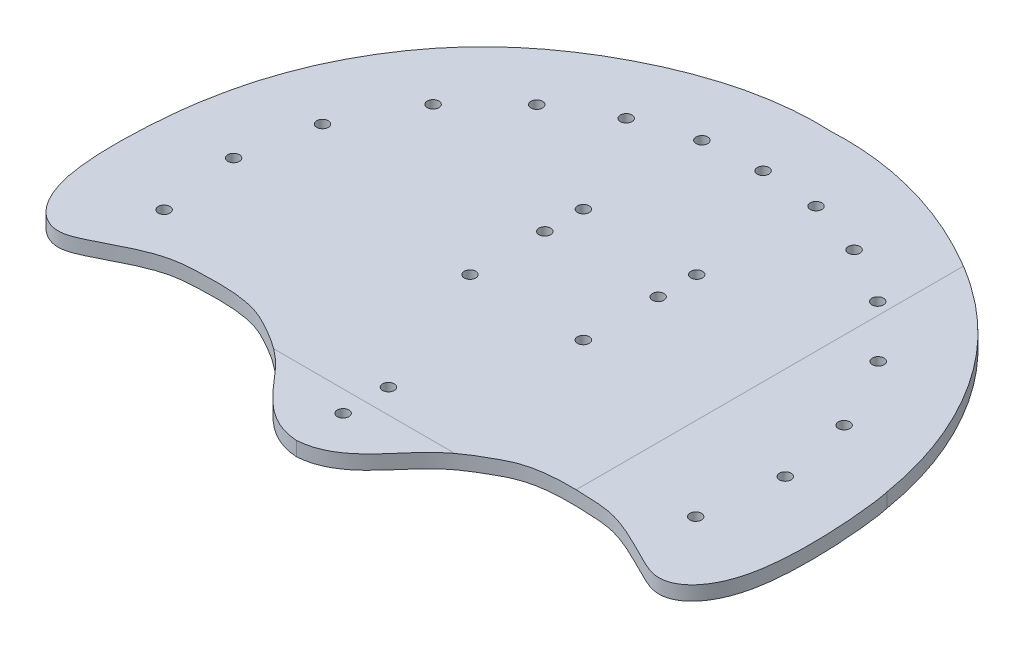
SolidWorks part; units mm, degrees
material "6061-T6 (SS)"
ref_plane "Front Plane" through (0, 0, 0) normal (0, 0, 1) x (1, 0, 0)
ref_plane "Top Plane" through (0, 0, 0) normal (0, 1, 0) x (1, 0, 0)
ref_plane "Right Plane" through (0, 0, 0) normal (1, 0, 0) x (0, 0, -1)
sketch "Sketch3" plane through (0, 0, 0) normal (0, 1, 0) x (1, 0, 0)
  line L0 (0, 0) -> (0, 159.1899) construction
  line L1 (0, 0) -> (0, -140.5301) construction
  line L2 (0, 0) -> (-190.5, 0) construction
  line L3 (0, 0) -> (190.5, 0) construction
  spline S0 degree 3 poles (-190.5, 0) (-184.3927, 37.537) (-157.2613, 93.9641) (-82.3875, 146.6227) (-31.3114, 160.7999) (0, 159.1899) knots 0 0 0 0 0.424401 0.65637 1 1 1 1
  spline S1 degree 3 poles (-190.5, 0) (-192.064, -4.9635) (-201.9672, -83.3146) (-174.6966, -109.29) (-151.6301, -100.568) (-131.4108, -87.7198) (-96.8436, -85.3754) (-78.6925, -86.2588) (-58.8335, -96.8794) (-37.3059, -109.9358) (-21.3496, -139.1148) (0, -140.5301) knots 0 0 0 0 0.166997 0.292321 0.319633 0.426735 0.458914 0.609242 0.64191 0.766802 1 1 1 1
  spline S2 degree 3 poles (190.5, 0) (192.064, -4.9635) (201.9672, -83.3146) (174.6966, -109.29) (151.6301, -100.568) (131.4108, -87.7198) (96.8436, -85.3754) (78.6925, -86.2588) (58.8335, -96.8794) (37.3059, -109.9358) (21.3496, -139.1148) (0, -140.5301) knots 0 0 0 0 0.166997 0.292321 0.319633 0.426735 0.458914 0.609242 0.64191 0.766802 1 1 1 1
  spline S3 degree 3 poles (190.5, 0) (184.3927, 37.537) (157.2613, 93.9641) (82.3875, 146.6227) (31.3114, 160.7999) (0, 159.1899) knots 0 0 0 0 0.424401 0.65637 1 1 1 1
  dimension "D1" = 381
  dimension "D2" = 299.72
  dimension "D3" = 159.1899
  dimension "D4" = 86.8953
  dimension "D5" = 104.4979
  dimension "D6" = 29.1616
  dimension "D7" = 92.2742
  dimension "D8" = 108.411
  dimension "D9" = 67.4883
  dimension "D10" = 43.7314
  dimension "D11" = 117.6915
  dimension "D12" = 162.2568
  dimension "D13" = 89.4522
  dimension "D14" = 140.1036
  dimension "D15" = 175.0666
  dimension "D16" = 50.2669
  dimension "D17" = 101.3666
  dimension "D18" = 138.1225
  dimension "D19" = 155.1557
  dimension "D20" = 192.0074
  dimension "D21" = 193.9268
  dimension "D23" = 76.6666
extrude "Boss-Extrude1" add sketch "Sketch3" along normal blind 7.9502 from surface starting at plane "Top Plane"
sketch "Sketch5" plane through (0, 0, 0) normal (0, -1, 0) x (1, 0, 0)
  line L0 (0, 0) -> (0, -20.32) construction
  line L1 (31.75, -52.07) -> (-31.75, -52.07)
  line L2 (31.75, -52.07) -> (31.75, 11.43)
  line L3 (31.75, 11.43) -> (-31.75, 11.43)
  line L4 (-31.75, -52.07) -> (-31.75, 11.43)
  line L5 (31.75, -52.07) -> (-31.75, 11.43) construction
  line L6 (31.75, 11.43) -> (-31.75, -52.07) construction
  line L7 (-31.75, -52.07) -> (-31.75, -30.48)
  line L8 (-31.75, -30.48) -> (31.75, -30.48) construction
  line L9 (0, -20.32) -> (140.7253, -20.32) construction
  line L10 (0, -20.32) -> (0, -97.1287) construction
  line L11 (0, -20.32) -> (31.9753, -118.7297) construction
  line L13 (0, -20.32) -> (63.8443, -108.1942) construction
  line L14 (0, -20.32) -> (95.5392, -89.7333) construction
  line L15 (124.7166, -60.8429) -> (0, -20.32) construction
  line L16 (0, -20.32) -> (154.5508, 21.0918) construction
  line L17 (0, -20.32) -> (148.922, 65.6601) construction
  line L18 (0, -20.32) -> (-31.9753, -118.7297) construction
  line L19 (0, -20.32) -> (-63.8443, -108.1942) construction
  line L20 (0, -20.32) -> (-95.5392, -89.7333) construction
  line L21 (-124.7166, -60.8429) -> (0, -20.32) construction
  line L22 (0, -20.32) -> (-154.5508, 21.0918) construction
  line L23 (0, -20.32) -> (-148.922, 65.6601) construction
  spline S0 degree 3 poles (-148.922, 65.6601) (-157.8584, 40.2253) (-156.2837, 8.5854) (-143.1202, -28.9506) (-139.3242, -37.3463) (-130.3709, -53.1962) (-125.215, -60.649) (-118.0488, -69.1403) (-116.5795, -70.7975) (-113.5719, -74.0252) (-112.0368, -75.592) (-107.2801, -80.2116) (-103.9215, -83.1695) (-93.3361, -91.6595) (-85.5959, -96.8074) (-76.3408, -101.9556) (-75.3049, -102.5187) (-73.219, -103.6268) (-72.1677, -104.1726) (-69.0049, -105.7765) (-66.8862, -106.8006) (-60.5068, -109.7299) (-56.2231, -111.4921) (-47.6308, -114.6027) (-43.3223, -115.9511) (-34.7104, -118.209) (-30.4072, -119.1185) (-21.8242, -120.4791) (-17.5446, -120.9304) (-11.1443, -121.2499) (-9.0138, -121.2968) (-5.8216, -121.2757) (-4.1848, -121.2414) (-2.5489, -121.1705) (-1.9677, -121.1408) (-1.9605, -121.1404) (-1.2995, -121.1064) (-0.6497, -121.073) (0, -121.0396) knots -0.292878 -0.292878 -0.292878 -0.292878 0.125 0.125 0.25 0.25 0.375 0.375 0.40625 0.40625 0.4375 0.4375 0.5 0.5 0.625 0.625 0.640625 0.640625 0.65625 0.65625 0.6875 0.6875 0.75 0.75 0.8125 0.8125 0.875 0.875 0.9375 0.9375 0.96875 0.96875 0.984375 0.992798 0.992798 0.99292 0.99292 1 1 1 1
  spline S5 degree 3 poles (998.6789, -69.6893) (665.1581, -86.8384) (331.6156, -103.9885) (-1.9268, -121.1387) (-1.9605, -121.1404) (-1.9677, -121.1408) (-2.5489, -121.1705) (-4.1848, -121.2414) (-5.8216, -121.2757) (-9.0138, -121.2968) (-11.1443, -121.2499) (-17.5446, -120.9304) (-21.8242, -120.4791) (-30.4072, -119.1185) (-34.7104, -118.209) (-43.3223, -115.9511) (-47.6308, -114.6027) (-56.2231, -111.4921) (-60.5068, -109.7299) (-66.8862, -106.8006) (-69.0049, -105.7765) (-72.1677, -104.1726) (-73.219, -103.6268) (-75.3049, -102.5187) (-76.3408, -101.9556) (-85.5959, -96.8074) (-93.3361, -91.6595) (-103.9215, -83.1695) (-107.2801, -80.2116) (-112.0368, -75.592) (-113.5719, -74.0252) (-116.5795, -70.7975) (-118.0488, -69.1403) (-125.215, -60.649) (-130.3709, -53.1962) (-139.3242, -37.3463) (-143.1202, -28.9506) (-198.5095, 128.9933) (-22.362, 351.6373) (651.8169, -587.5188) knots -3.627409 -3.627409 -3.627409 -3.627409 0.006836 0.00708 0.00708 0.007202 0.007202 0.015625 0.03125 0.03125 0.0625 0.0625 0.125 0.125 0.1875 0.1875 0.25 0.25 0.3125 0.3125 0.34375 0.34375 0.359375 0.359375 0.375 0.375 0.5 0.5 0.5625 0.5625 0.59375 0.59375 0.625 0.625 0.75 0.75 0.875 0.875 3.034324 3.034324 3.034324 3.034324 only from (0, -121.0396) to (-152.8945, 6.1184)
  spline S6 degree 3 poles (-1687.8289, -2297.0686) (-150.4269, 537.0593) (218.9922, 187.4002) (143.1202, -28.9506) (139.3242, -37.3463) (130.3709, -53.1962) (125.215, -60.649) (118.0488, -69.1403) (116.5795, -70.7975) (113.5719, -74.0252) (112.0368, -75.592) (107.2801, -80.2116) (103.9215, -83.1695) (93.3361, -91.6595) (85.5959, -96.8074) (76.3408, -101.9556) (75.3049, -102.5187) (73.219, -103.6268) (72.1677, -104.1726) (69.0049, -105.7765) (66.8862, -106.8006) (60.5068, -109.7299) (56.2231, -111.4921) (47.6308, -114.6027) (43.3223, -115.9511) (34.7104, -118.209) (30.4072, -119.1185) (21.8242, -120.4791) (17.5446, -120.9304) (11.1443, -121.2499) (9.0138, -121.2968) (5.8216, -121.2757) (4.1848, -121.2414) (2.5489, -121.1705) (1.9677, -121.1408) (1.9605, -121.1404) (-997.3522, -69.7575) (-1996.6535, -18.3753) (-2996.029, 33.0152) knots -2.879056 -2.879056 -2.879056 -2.879056 0.125 0.125 0.25 0.25 0.375 0.375 0.40625 0.40625 0.4375 0.4375 0.5 0.5 0.625 0.625 0.640625 0.640625 0.65625 0.65625 0.6875 0.6875 0.75 0.75 0.8125 0.8125 0.875 0.875 0.9375 0.9375 0.96875 0.96875 0.984375 0.992798 0.992798 0.99292 0.99292 11.881939 11.881939 11.881939 11.881939 only from (152.8945, 6.1184) to (0, -121.0396)
  spline S8 degree 3 poles (148.922, 65.6601) (157.8584, 40.2253) (156.2837, 8.5854) (143.1202, -28.9506) (139.3242, -37.3463) (130.3709, -53.1962) (125.215, -60.649) (118.0488, -69.1403) (116.5795, -70.7975) (113.5719, -74.0252) (112.0368, -75.592) (107.2801, -80.2116) (103.9215, -83.1695) (93.3361, -91.6595) (85.5959, -96.8074) (76.3408, -101.9556) (75.3049, -102.5187) (73.219, -103.6268) (72.1677, -104.1726) (69.0049, -105.7765) (66.8862, -106.8006) (60.5068, -109.7299) (56.2231, -111.4921) (47.6308, -114.6027) (43.3223, -115.9511) (34.7104, -118.209) (30.4072, -119.1185) (21.8242, -120.4791) (17.5446, -120.9304) (11.1443, -121.2499) (9.0138, -121.2968) (5.8216, -121.2757) (4.1848, -121.2414) (2.5489, -121.1705) (1.9677, -121.1408) (1.9605, -121.1404) (1.2995, -121.1064) (0.6497, -121.073) (0, -121.0396) knots -0.292878 -0.292878 -0.292878 -0.292878 0.125 0.125 0.25 0.25 0.375 0.375 0.40625 0.40625 0.4375 0.4375 0.5 0.5 0.625 0.625 0.640625 0.640625 0.65625 0.65625 0.6875 0.6875 0.75 0.75 0.8125 0.8125 0.875 0.875 0.9375 0.9375 0.96875 0.96875 0.984375 0.992798 0.992798 0.99292 0.99292 1 1 1 1
  point P0 (0, -20.32)
  point P3 (0, -20.32)
  point P14 (0, 114.3)
  point P16 (0, 88.9)
  dimension "D2" = 63.5
  dimension "D3" = 63.5
  dimension "D4" = 21.59
  dimension "D6" = 25.4
  dimension "D7" = 88.9
  dimension "D8" = 18
  dimension "D9" = 18
  dimension "D10" = 18
  dimension "D11" = 18
  dimension "D12" = 15
  dimension "D13" = 15
  dimension "D5" = 38.1
hole_wizard "F (0.257) Diameter Hole2" positions "Sketch6" profile "Sketch7" hole size "F" standard "ANSI Inch" end condition through all
sketch "Sketch6" plane through (0, 0, 0) normal (0, -1, 0) x (-1, 0, 0)
  line L0 (200000, 20.32) -> (-200140.7253, 20.32) construction
  spline S0 degree 3 poles (-148.922, -65.6601) (-157.8584, -40.2253) (-156.2837, -8.5854) (-143.1202, 28.9506) (-139.3242, 37.3463) (-130.3709, 53.1962) (-125.215, 60.649) (-118.0488, 69.1403) (-116.5795, 70.7975) (-113.5719, 74.0252) (-112.0368, 75.592) (-107.2801, 80.2116) (-103.9215, 83.1695) (-93.3361, 91.6595) (-85.5959, 96.8074) (-76.3408, 101.9556) (-75.3049, 102.5187) (-73.219, 103.6268) (-72.1677, 104.1726) (-69.0049, 105.7765) (-66.8862, 106.8006) (-60.5068, 109.7299) (-56.2231, 111.4921) (-47.6308, 114.6027) (-43.3223, 115.9511) (-34.7104, 118.209) (-30.4072, 119.1185) (-21.8242, 120.4791) (-17.5446, 120.9304) (-11.1443, 121.2499) (-9.0138, 121.2968) (-5.8216, 121.2757) (-4.1848, 121.2414) (-2.5489, 121.1705) (-1.9677, 121.1408) (-1.9605, 121.1404) (-1.2995, 121.1064) (-0.6497, 121.073) (0, 121.0396) knots -0.292878 -0.292878 -0.292878 -0.292878 0.125 0.125 0.25 0.25 0.375 0.375 0.40625 0.40625 0.4375 0.4375 0.5 0.5 0.625 0.625 0.640625 0.640625 0.65625 0.65625 0.6875 0.6875 0.75 0.75 0.8125 0.8125 0.875 0.875 0.9375 0.9375 0.96875 0.96875 0.984375 0.992798 0.992798 0.99292 0.99292 1 1 1 1 construction
  spline S1 degree 3 poles (148.922, -65.6601) (157.8584, -40.2253) (156.2837, -8.5854) (143.1202, 28.9506) (139.3242, 37.3463) (130.3709, 53.1962) (125.215, 60.649) (118.0488, 69.1403) (116.5795, 70.7975) (113.5719, 74.0252) (112.0368, 75.592) (107.2801, 80.2116) (103.9215, 83.1695) (93.3361, 91.6595) (85.5959, 96.8074) (76.3408, 101.9556) (75.3049, 102.5187) (73.219, 103.6268) (72.1677, 104.1726) (69.0049, 105.7765) (66.8862, 106.8006) (60.5068, 109.7299) (56.2231, 111.4921) (47.6308, 114.6027) (43.3223, 115.9511) (34.7104, 118.209) (30.4072, 119.1185) (21.8242, 120.4791) (17.5446, 120.9304) (11.1443, 121.2499) (9.0138, 121.2968) (5.8216, 121.2757) (4.1848, 121.2414) (2.5489, 121.1705) (1.9677, 121.1408) (1.9605, 121.1404) (1.2995, 121.1064) (0.6497, 121.073) (0, 121.0396) knots -0.292878 -0.292878 -0.292878 -0.292878 0.125 0.125 0.25 0.25 0.375 0.375 0.40625 0.40625 0.4375 0.4375 0.5 0.5 0.625 0.625 0.640625 0.640625 0.65625 0.65625 0.6875 0.6875 0.75 0.75 0.8125 0.8125 0.875 0.875 0.9375 0.9375 0.96875 0.96875 0.984375 0.992798 0.992798 0.99292 0.99292 1 1 1 1 construction
  point P3 (31.75, 52.07)
  point P6 (31.75, -11.43)
  point P9 (-31.75, -11.43)
  point P15 (31.75, 30.48)
  point P32 (-31.75, 30.48)
  point P39 (-31.75, 52.07)
  point P42 (-154.5508, -21.0918)
  point P45 (-148.922, -65.6601)
  point P48 (-146.1469, 20.32)
  point P54 (-124.7166, 60.8429)
  point P57 (-95.5392, 89.7333)
  point P60 (148.922, -65.6601)
  point P63 (154.5508, -21.0918)
  point P66 (124.7166, 60.8429)
  point P69 (95.5392, 89.7333)
  point P72 (63.8443, 108.1942)
  point P76 (31.9753, 118.7297)
  point P79 (0, 121.0396)
  point P82 (-31.9753, 118.7297)
  point P85 (-63.8443, 108.1942)
  point P88 (-95.5392, 89.7333)
  point P91 (146.1469, 20.32)
  point P95 (0, -88.9)
  point P98 (0, -114.3)
sketch "Sketch7" plane through (-31.75, 0, -52.07) normal (1, 0, 0) x (0, 0, -1)
  line L0 (0, 0) -> (0, 7.9502)
  line L1 (0, 7.9502) -> (3.2639, 7.9502)
  line L2 (3.2639, 7.9502) -> (3.2639, 0)
  line L5 (3.2639, 0) -> (0, 0)
  line L11 (0, -6.35) -> (0, 107.95) construction
  dimension "Thru Hole Dia." = 6.5278
  dimension "Thru Hole Depth" = 7.9502
sketch "Sketch9" plane through (0, 7.9502, 0) normal (0, 1, 0) x (1, 0, 0)
  line L0 (102.3823, -86.0787) -> (102.3823, 130.9193)
  line L1 (-50.7649, -102.4301) -> (50.7649, -102.4301)
  spline S0 degree 3 poles (0, -140.5301) (21.3496, -139.1148) (37.3059, -109.9358) (58.8335, -96.8794) (78.6925, -86.2588) (96.8436, -85.3754) (131.4108, -87.7198) (151.6301, -100.568) (174.6966, -109.29) (201.9672, -83.3146) (192.064, -4.9635) (190.5, 0) knots 0 0 0 0 0.233198 0.35809 0.390758 0.541086 0.573265 0.680367 0.707679 0.833003 1 1 1 1 construction
  spline S1 degree 3 poles (190.5, 0) (184.3927, 37.537) (157.2613, 93.9641) (82.3875, 146.6227) (31.3114, 160.7999) (0, 159.1899) knots 0 0 0 0 0.424401 0.65637 1 1 1 1 construction
  spline S2 degree 3 poles (-190.5, 0) (-192.064, -4.9635) (-201.9672, -83.3146) (-174.6966, -109.29) (-151.6301, -100.568) (-131.4108, -87.7198) (-96.8436, -85.3754) (-78.6925, -86.2588) (-58.8335, -96.8794) (-37.3059, -109.9358) (-21.3496, -139.1148) (0, -140.5301) knots 0 0 0 0 0.166997 0.292321 0.319633 0.426735 0.458914 0.609242 0.64191 0.766802 1 1 1 1 construction
  dimension "D1" = 38.1
split line "Split Line1"
equation "\"Plate thickness\"=0.313"
equation "\"D1@Boss-Extrude1\"=\"Plate thickness\""
equation "\"Bracket Alignment\"= .80"
equation "\"D1@Sketch5\"=\"Bracket Alignment\""
